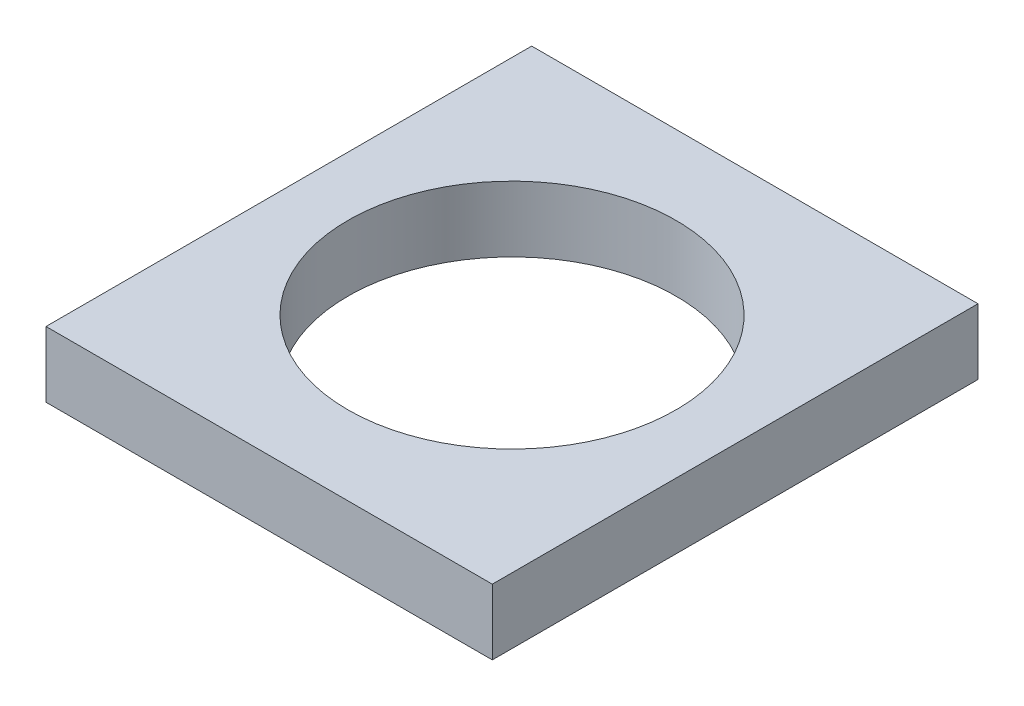
SolidWorks part; units mm, degrees
ref_plane "Alzado" through (0, 0, 0) normal (0, 0, 1) x (1, 0, 0)
ref_plane "Planta" through (0, 0, 0) normal (0, 1, 0) x (1, 0, 0)
ref_plane "Vista lateral" through (0, 0, 0) normal (1, 0, 0) x (0, 0, -1)
sketch "Croquis1" plane through (0, 0, 0) normal (0, 1, 0) x (1, 0, 0)
  line L1 (-17, -18.5) -> (17, -18.5)
  line L2 (-17, -18.5) -> (-17, 18.5)
  line L3 (-17, 18.5) -> (17, 18.5)
  line L4 (17, -18.5) -> (17, 18.5)
  line L5 (-17, -18.5) -> (17, 18.5) construction
  line L6 (-17, 18.5) -> (17, -18.5) construction
  point P0 (0, 0)
  dimension "D1" = 34
  dimension "D2" = 37
sheet metal parameters "Chapa metálica1" thickness 5 parameters "D1"=0.7366, "Espesor"=5
base flange "Brida base1" sketch "Croquis1" thickness 5 reverse thickness direction no parameters "D1"=0.7366
sketch "Croquis5" plane through (0, 0, 0) normal (0, 1, 0) x (1, 0, 0)
  circle A0 centre (0, 0) radius 12.5
  dimension "D1" = 25
extrude "Cortar-Extruir1" cut sketch "Croquis5" against normal through all normal cut yes
flat pattern "Chapa desplegada1" [suppressed]
sketch "Líneas de pliegue1" plane through (0, 0, 0) normal (0, 1, 0) x (-1, 0, 0)
sketch3d "Cuadro delimitador1" [suppressed]
  line L0 (-34, 37, 0) -> (-34, 0, 0) construction
  line L1 (0, 37, 0) -> (0, 0, 0) construction
  line L2 (-34, 37, 0) -> (0, 37, 0) construction
  line L3 (-34, 0, 0) -> (0, 0, 0) construction
